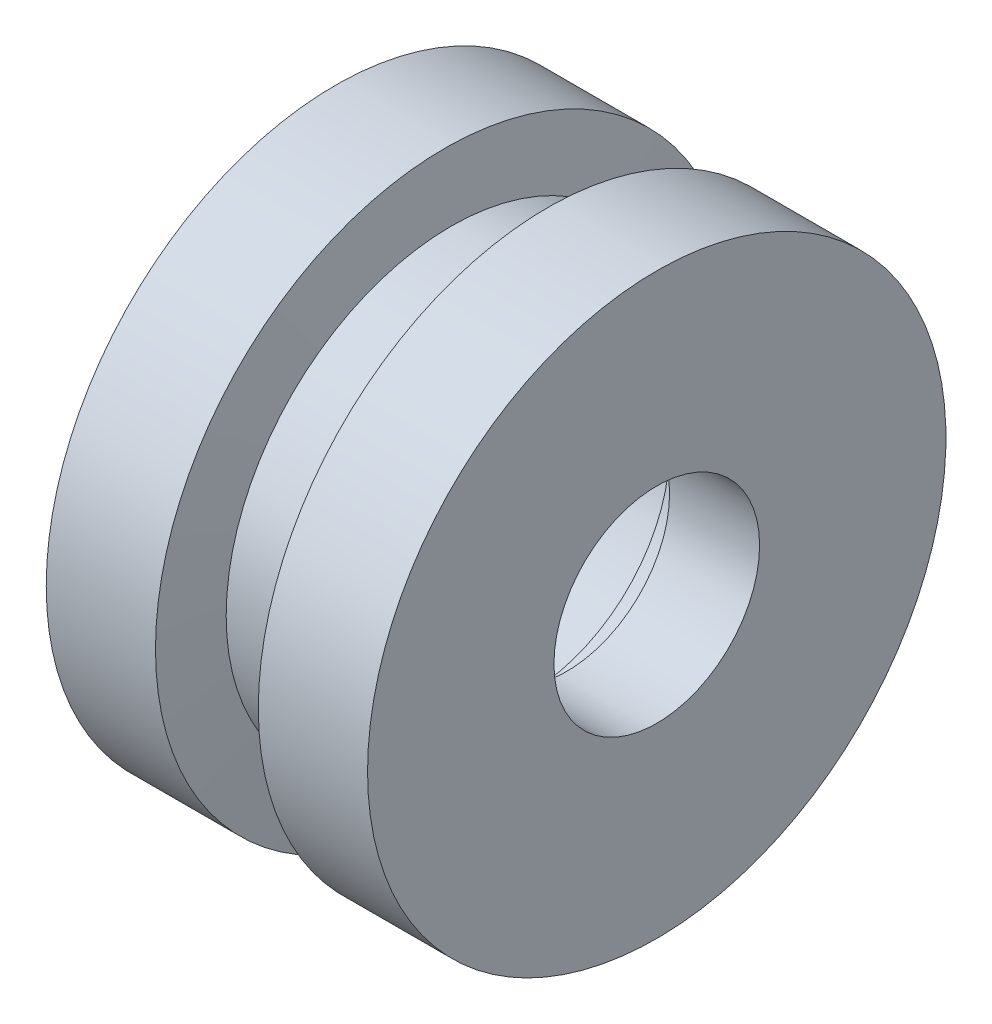
SolidWorks part; units mm, degrees
ref_plane "Front Plane" through (0, 0, 0) normal (0, 0, 1) x (1, 0, 0)
ref_plane "Top Plane" through (0, 0, 0) normal (0, 1, 0) x (1, 0, 0)
ref_plane "Right Plane" through (0, 0, 0) normal (1, 0, 0) x (0, 0, -1)
sketch "Sketch1" plane through (0, 0, 0) normal (0, 1, 0) x (1, 0, 0)
  line L0 (0, 0) -> (25, 0) construction
  line L2 (0, 22.5) -> (25, 22.5)
  line L3 (0, 22.5) -> (0, 12)
  line L4 (0, 12) -> (15, 12)
  line L5 (25, 22.5) -> (25, 12)
  line L13 (15, 12) -> (15, 11)
  line L14 (15, 11) -> (18, 11)
  line L15 (25, 11) -> (25, 12)
  line L18 (25, 11) -> (25, 8)
  line L19 (25, 8) -> (18, 8)
  line L20 (18, 11) -> (18, 8)
  dimension "D1" = 24
  dimension "D2" = 45
  dimension "D3" = 25
  dimension "D4" = 1
  dimension "D5" = 15
  dimension "D6" = 16
  dimension "D7" = 3
revolve "Revolve1" add sketch "Sketch1" angle 360 about L0
sketch "Sketch4" plane through (0, 0, 0) normal (0, 1, 0) x (1, 0, 0)
  line L0 (8.5, 22.5) -> (9, 17.5)
  line L1 (25, 22.5) -> (0, 22.5) construction
  line L2 (9, 17.5) -> (16, 17.5)
  line L3 (16, 17.5) -> (16.5, 22.5)
  line L4 (25, 22.5) -> (0, 22.5) construction
  line L5 (16.5, 22.5) -> (8.5, 22.5)
  line L6 (12.5, 22.5) -> (12.5, 17.5) construction
  line L7 (25, 22.5) -> (0, 22.5) construction
  line L8 (0, 0) -> (25, 0) construction
  line L9 (0, 22.5) -> (0, -22.5) construction
  line L10 (25, -22.5) -> (25, 22.5) construction
  point P10 (12.5, 0)
  dimension "D1" = 8
  dimension "D2" = 5
  dimension "D3" = 7
revolve "Cut-Revolve1" cut sketch "Sketch4" angle 360 about L8
move or copy body "Body-Move/Copy1" [suppressed] bodies to move or copy 102
